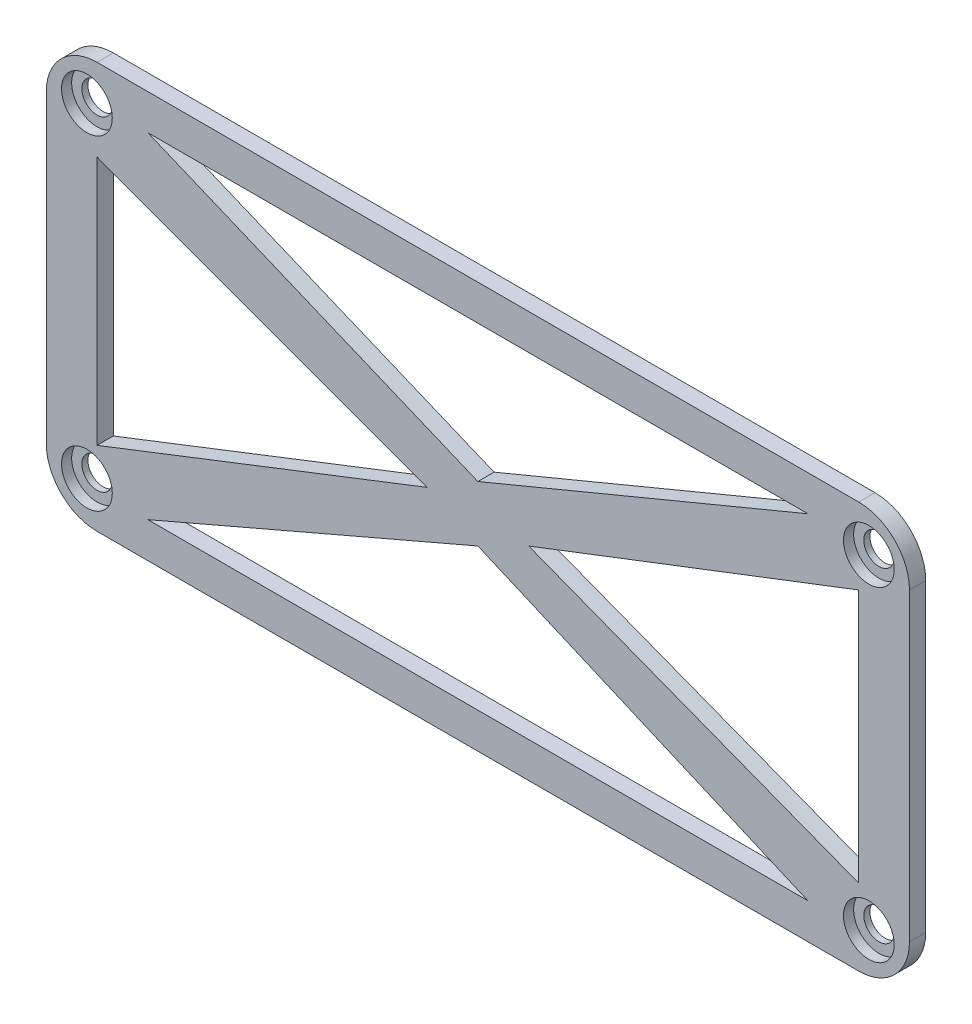
SolidWorks part; units mm, degrees
ref_plane "前视基准面" through (0, 0, 0) normal (0, 0, 1) x (1, 0, 0)
ref_plane "上视基准面" through (0, 0, 0) normal (0, 1, 0) x (1, 0, 0)
ref_plane "右视基准面" through (0, 0, 0) normal (1, 0, 0) x (0, 0, -1)
sketch "草图1" plane through (0, 0, 0) normal (0, 0, 1) x (1, 0, 0)
  line L1 (-72.5741, 35.4874) -> (77.4259, 35.4874)
  line L2 (-82.5741, 25.4874) -> (-82.5741, -34.5126)
  line L3 (-72.5741, -44.5126) -> (77.4259, -44.5126)
  line L4 (87.4259, 25.4874) -> (87.4259, -34.5126)
  arc A0 (-72.5741, 35.4874) -> (-82.5741, 25.4874) centre (-72.5741, 25.4874) ccw
  arc A1 (-72.5741, -44.5126) -> (-82.5741, -34.5126) centre (-72.5741, -34.5126) cw
  arc A2 (87.4259, 25.4874) -> (77.4259, 35.4874) centre (77.4259, 25.4874) ccw
  arc A3 (87.4259, -34.5126) -> (77.4259, -44.5126) centre (77.4259, -34.5126) cw
  dimension "D1" = 10
  dimension "D2" = 10
  dimension "D3" = 10
  dimension "D4" = 10
  dimension "D5" = 80
  dimension "D6" = 170
extrude "凸台-拉伸1" add sketch "草图1" along normal blind 3.2
ref_plane "for screw hole" through (0, 0, 3.2) normal (0, 0, 1) x (1, 0, 0)
sketch "草图2" plane through (0, 0, 3.2) normal (0, 0, 1) x (1, 0, 0)
  line L0 (77.4259, 35.4874) -> (-72.5741, 35.4874) construction
  line L1 (-82.5741, 25.4874) -> (-82.5741, -34.5126) construction
  line L2 (-72.5741, -44.5126) -> (77.4259, -44.5126) construction
  line L3 (87.4259, -34.5126) -> (87.4259, 25.4874) construction
  line L4 (-62.5741, 28.4874) -> (2.4259, 1.4874)
  line L6 (-72.5741, 19.3263) -> (-7.5741, -4.5126)
  line L8 (2.4259, -9.5126) -> (-62.5741, -37.5126)
  line L10 (67.4259, -37.5126) -> (2.4259, -9.5126)
  line L12 (-72.5741, -29.8439) -> (-7.5741, -4.5126)
  line L13 (-72.5741, 19.3263) -> (-72.5741, -29.8439)
  line L15 (-62.5741, -37.5126) -> (67.4259, -37.5126)
  line L17 (67.4259, 28.4874) -> (2.4259, 1.4874)
  line L19 (-62.5741, 28.4874) -> (67.4259, 28.4874)
  line L21 (12.4259, -4.5126) -> (77.4259, 20.4874)
  line L25 (12.4259, -4.5126) -> (77.4259, -29.5126)
  line L26 (77.4259, -29.5126) -> (77.4259, 20.4874)
  circle A0 centre (-74.5741, 27.4874) radius 3
  circle A1 centre (-74.5741, -36.5126) radius 3
  circle A2 centre (79.4259, 27.4874) radius 3
  circle A3 centre (79.4259, -36.5126) radius 3
  point P17 (0, 0)
  point P18 (0, 0)
  point P19 (-62.5741, 20.4874)
  point P23 (77.4259, 20.4874)
  point P38 (2.4259, 1.4874)
  point P39 (-7.5741, -4.5126)
  point P40 (67.4259, 28.4874)
  point P41 (-62.5741, 28.4874)
  point P42 (2.4259, -9.5126)
  point P43 (12.4259, -4.5126)
  point P45 (-72.5741, -29.8439)
  point P46 (-62.5741, -37.5126)
  point P47 (67.4259, -37.5126)
  point P48 (77.4259, -29.5126)
  dimension "D2" = 6
  dimension "D3" = 6
  dimension "D4" = 6
  dimension "D8" = 8
  dimension "D9" = 8
  dimension "D10" = 8
  dimension "D11" = 6
  dimension "D14" = 75
  dimension "D5" = 8
  dimension "D6" = 8
  dimension "D7" = 8
  dimension "D12" = 8
  dimension "D13" = 8
  dimension "D15" = 75
  dimension "D16" = 34
  dimension "D20" = 7
  dimension "D21" = 7
  dimension "D22" = 20
  dimension "D23" = 20
  dimension "D24" = 20
  dimension "D25" = 10
  dimension "D26" = 7
  dimension "D27" = 20
  dimension "D28" = 15
  dimension "D29" = 15
  dimension "D30" = 10
  dimension "D31" = 10
  dimension "D32" = 15
  dimension "D33" = 7
  dimension "D34" = 20
extrude "切除-拉伸1" cut sketch "草图2" against normal blind 10 and the other way blind 39
ref_plane "for outer screw hole" through (0, 0, 3.2) normal (0, 0, 1) x (1, 0, 0)
sketch "草图3" plane through (0, 0, 3.2) normal (0, 0, 1) x (1, 0, 0)
  circle A0 centre (-74.5741, 27.4874) radius 5
  circle A1 centre (79.4259, 27.4874) radius 5
  circle A2 centre (79.4259, -36.5126) radius 5
  circle A3 centre (-74.5741, -36.5126) radius 5
  dimension "D1" = 10
  dimension "D2" = 10
  dimension "D3" = 10
  dimension "D4" = 10
extrude "切除-拉伸2" cut sketch "草图3" against normal blind 2
ref_plane "for stands" through (0, 0, 3.2) normal (0, 0, 1) x (1, 0, 0)
